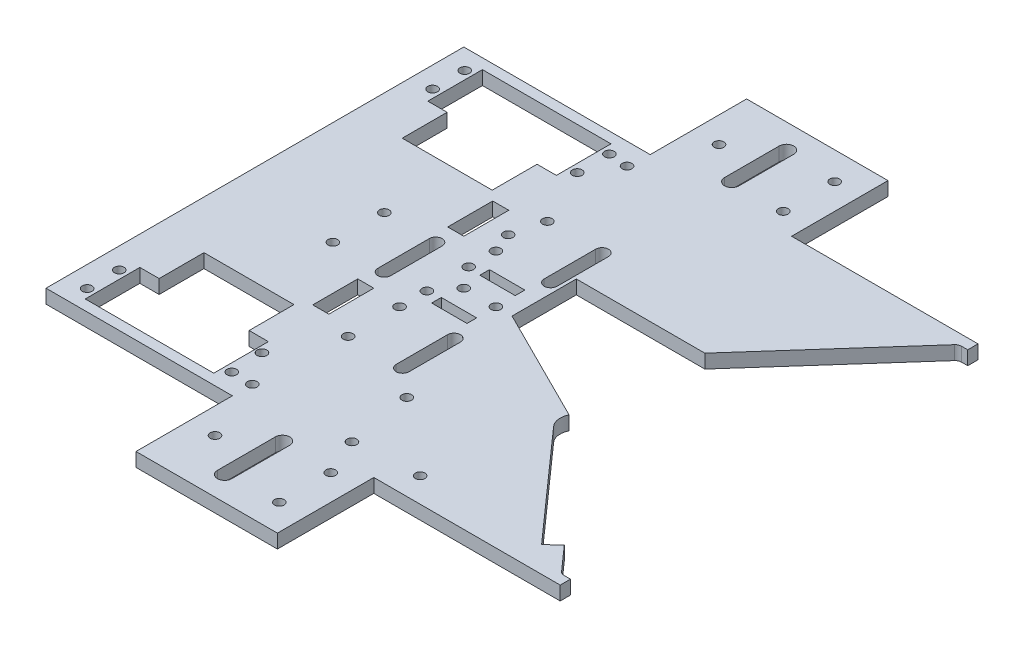
SolidWorks part; units mm, degrees
material "Acrylic (Medium-high impact)"
ref_plane "Front Plane" through (0, 0, 0) normal (0, 0, 1) x (1, 0, 0)
ref_plane "Top Plane" through (0, 0, 0) normal (0, 1, 0) x (1, 0, 0)
ref_plane "Right Plane" through (0, 0, 0) normal (1, 0, 0) x (0, 0, -1)
sketch "Sketch2" plane through (0, 0, 0) normal (0, 1, 0) x (1, 0, 0)
  line L2 (0, 0) -> (0, 65)
  line L3 (0, 65) -> (58, 65)
  line L4 (160, 0) -> (160, 65)
  line L8 (0, 0) -> (160, 0)
  line L9 (102, 65) -> (160, 65)
  line L11 (102, 65) -> (102, 95)
  line L12 (58, 65) -> (58, 95)
  line L13 (58, 95) -> (102, 95)
  dimension "D1" = 65
  dimension "D2" = 160
  dimension "D3" = 44
  dimension "D4" = 30
extrude "Boss-Extrude1" add sketch "Sketch2" along normal blind 4.3
mirror "Mirror1" about plane through (0, 4.3, 0) normal (0, 0, -1) of bodies 101
sketch "Sketch3" plane through (0, 4.3, 0) normal (0, 1, 0) x (1, 0, 0)
  line L0 (160, 61.8) -> (160, -61.8)
  line L1 (120.0126, 20) -> (157.1565, 61.8)
  line L3 (80.0126, 0) -> (80.0126, 20)
  line L4 (80.0126, 20) -> (120.0126, 20)
  line L12 (160, 65) -> (102, 65)
  line L13 (102, 65) -> (102, 95)
  line L15 (102, 95) -> (58, 95)
  line L16 (58, 65) -> (0, 65)
  line L17 (0, 65) -> (0, -65)
  line L18 (0, -65) -> (58, -65)
  line L20 (58, 95) -> (58, 65)
  line L22 (102, -65) -> (160, -65)
  line L23 (160, -65) -> (160, 65)
  line L36 (58, -65) -> (58, -95)
  line L38 (58, -95) -> (102, -95)
  line L39 (58, -95) -> (102, -95)
  line L40 (102, -95) -> (102, -65)
  line L42 (160, -61.8) -> (157.1556, -61.8)
  line L45 (160, 61.8) -> (157.1565, 61.8)
  line L48 (80.0126, 0) -> (120, -20)
  line L49 (120, -20) -> (157.1556, -61.8)
  line M24 (160, -65) -> (160, 65)
  dimension "D2" = 130
  dimension "D3" = 20
  dimension "D4" = 40
  dimension "D1" = 0
extrude "Cut-Extrude1" cut sketch "Sketch3" against normal blind 4.5 contours L48 L49 L1 L4 L3 M24 region at (132.7054, 4.3, -1.1594)
fillet "Fillet1" radius 2 2 edges at (157.1565, 2.15, -61.8) (157.1556, 2.15, 61.8)
ref_axis "Axis1" through (80, 4.3, 95) along (0, 0, -1)
sketch "Sketch4" plane through (0, 4.3, 0) normal (0, 1, 0) x (1, 0, 0)
  line L0 (80, -95) -> (80, 95)
  line L1 (102, -95) -> (58, -95) construction
  line L2 (102, 95) -> (58, 95) construction
ref_plane "Plane2" through (0, 4.3, 0) normal (0, 1, 0) x (1, 0, 0)
sketch "Sketch6" plane through (0, 4.3, 0) normal (0, 1, 0) x (1, 0, 0)
  line L3 (9, -61.8) -> (49, -61.8)
  line L6 (29, -45.8) -> (29, -44.8)
  line L7 (9, -44.8) -> (15, -44.8)
  line L11 (43, -44.8) -> (43, -30.8418)
  line L12 (15, -44.8) -> (15, -30.8418)
  line L13 (15, -30.8418) -> (43, -30.8418)
  line L15 (0, 0) -> (80.0126, 0)
  line L16 (80.0126, 0) -> (120, -20) construction
  line L18 (9, 44.8) -> (15, 44.8)
  line L20 (15, 30.8418) -> (43, 30.8418)
  line L21 (15, 44.8) -> (15, 30.8418)
  line L22 (43, 44.8) -> (43, 30.8418)
  line L25 (15, -45.8) -> (15, -30.8418) construction
  line L27 (9, 61.8) -> (49, 61.8)
  line L30 (4, -61.8) -> (3, -61.8)
  line L31 (0, -61.8) -> (160, -61.8) construction
  line L32 (3, -61.8) -> (4, -61.8)
  line L33 (3, -44.8) -> (3, -62.8) construction
  line L34 (3, -62.8) -> (55, -62.8) construction
  line L35 (55, -44.8) -> (55, -62.8) construction
  line L36 (4, -61.8) -> (54, -61.8) construction
  line L37 (0, 61.8) -> (160, 61.8) construction
  line L38 (54, 61.8) -> (55, 61.8)
  line L39 (54, 61.8) -> (55, 61.8)
  line L40 (43, 44.8) -> (49, 44.8)
  line L41 (4, -45.8) -> (4, -61.8) construction
  line L42 (4, -45.8) -> (54, -45.8) construction
  line L43 (43, -44.8) -> (49, -44.8)
  line L44 (3, -44.8) -> (55, -44.8) construction
  line L45 (29, -45.8) -> (29, -30.8418) construction
  line L46 (43, -45.8) -> (43, -30.8418) construction
  line L47 (54, -45.8) -> (54, -61.8) construction
  line L48 (9, -61.8) -> (49, -61.8)
  line L52 (9, 61.8) -> (9, 44.8)
  line L53 (55, 61.8) -> (54, 61.8)
  line L56 (49, 61.8) -> (49, 44.8)
  line L59 (3, -61.8) -> (4, -61.8)
  line L60 (9, -44.8) -> (9, -61.8)
  line L64 (49, -44.8) -> (49, -61.8)
  dimension "D4" = 1
  dimension "D5" = 14
  dimension "D6" = 14
extrude "Cut-Extrude2" cut sketch "Sketch6" against normal blind 10
sketch "Sketch8" plane through (0, 4.3, 0) normal (0, 1, 0) x (1, 0, 0)
  circle A0 centre (6.5, 58.8) radius 1.5
  circle A1 centre (6.5, 48.8) radius 1.5
  circle A2 centre (51.5, 48.8) radius 1.5
  circle A3 centre (51.5, 58.8) radius 1.5
  circle A4 centre (6.5, -48.7) radius 1.5
  circle A5 centre (6.5, -58.7) radius 1.5
  circle A6 centre (51.5, -58.7) radius 1.5
  circle A7 centre (51, -48.8) radius 1.5
  dimension "D7" = 3
extrude "Cut-Extrude3" cut sketch "Sketch8" against normal blind 10
sketch "Sketch9" plane through (0, 0, 0) normal (0, -1, 0) x (1, 0, 0)
  line L0 (75.75, 69.4) -> (75.75, 87.4)
  line L1 (75.75, -87.4) -> (75.75, -70.4)
  line L2 (80.25, -87.4) -> (80.25, -70.4)
  line L4 (80.25, 69.4) -> (80.25, 87.4)
  circle A0 centre (94, 70.4) radius 1.5
  circle A1 centre (66, 78.4) radius 1.5
  circle A2 centre (66, -78.4) radius 1.5
  circle A3 centre (94, -86.4) radius 1.5
  circle A4 centre (94, 86.4) radius 1.5
  circle A5 centre (94, -70.4) radius 1.5
  arc A6 (75.75, -87.4) -> (80.25, -87.4) centre (78, -87.4) ccw
  arc A7 (80.25, -70.4) -> (75.75, -70.4) centre (78, -70.4) ccw
  arc A10 (75.75, 69.4) -> (80.25, 69.4) centre (78, 69.4) ccw
  arc A12 (80.25, 87.4) -> (75.75, 87.4) centre (78, 87.4) ccw
  dimension "D1" = 3
extrude "Cut-Extrude4" cut sketch "Sketch9" against normal blind 10
sketch "Sketch7" plane through (0, 4.3, 0) normal (0, 1, 0) x (1, 0, 0)
  line L0 (0, 0) -> (80.0126, 0)
  line L1 (0, 65) -> (0, -65) construction
  line L2 (80.0126, 0) -> (80.0126, 20) construction
  line L3 (80, -95) -> (80, 95) construction
  line L4 (64, -9) -> (75, -9)
  line L5 (64, -6) -> (75, -6)
  line L6 (64, -9) -> (64, -6)
  line L7 (75, -9) -> (75, -6)
  line L8 (64, -7.5) -> (75, -7.5)
  line L9 (64, 7.5) -> (75, 7.5)
  line L10 (75, 9) -> (75, 6)
  line L11 (64, 9) -> (64, 6)
  line L12 (64, 6) -> (75, 6)
  line L13 (64, 9) -> (75, 9)
  circle A0 centre (60.0126, -6.5) radius 1.5
  circle A1 centre (60.0126, 6.5) radius 1.5
  dimension "D1" = 3
  dimension "D2" = 6.5
  dimension "D3" = 20
  dimension "D6" = 11
  dimension "D4" = 5
  dimension "D5" = 3
  dimension "D7" = 7.5
sketch "Sketch10" plane through (0, 4.3, 0) normal (0, 1, 0) x (1, 0, 0)
  line L0 (120, -20) -> (156.5589, -61.1287) construction
  line L1 (123.3218, -23.737) -> (149.8964, -53.6334)
  line L2 (116.263, -23.3218) -> (146.1593, -56.9552)
  line L3 (149.8964, -53.6334) -> (146.1593, -56.9552)
  line L4 (120, -20) -> (156.5589, -61.1287) construction
  line L5 (116.263, -23.3218) -> (152.8218, -64.4505) construction
  arc A0 (123.3218, -23.737) -> (116.263, -23.3218) centre (120, -20) ccw
  dimension "D1" = 5
  dimension "D2" = 45
extrude "Cut-Extrude5" cut sketch "Sketch10" against normal blind 10
sketch "Sketch11" plane through (0, 0, 0) normal (0, -1, 0) x (1, 0, 0)
  line L0 (0, 0) -> (80.0126, 0) construction
  line L1 (80, 95) -> (80, -95) construction
  line L2 (80.0126, 0) -> (0, 0)
  line L4 (75, 31.0313) -> (75, 15.0313)
  line L6 (79, 31.0313) -> (79, 15.0313)
  line L7 (79, -31.0313) -> (79, -15.0313)
  line L8 (75, -31.0313) -> (75, -15.0313)
  circle A0 centre (60, 31) radius 1.5
  circle A1 centre (60, 15) radius 1.5
  arc A2 (75, 31.0313) -> (79, 31.0313) centre (77, 31.0313) cw
  arc A3 (75, 15.0313) -> (79, 15.0313) centre (77, 15.0313) ccw
  arc A4 (75, -15.0313) -> (79, -15.0313) centre (77, -15.0313) cw
  arc A5 (75, -31.0313) -> (79, -31.0313) centre (77, -31.0313) ccw
  circle A6 centre (60, -15) radius 1.5
  circle A7 centre (60, -31) radius 1.5
  dimension "D1" = 3
  dimension "D2" = 16
  dimension "D3" = 15
  dimension "D4" = 20
  dimension "D5" = 15
  dimension "D6" = 4
extrude "Cut-Extrude6" cut sketch "Sketch11" against normal blind 10 contours L4 A3 L6 A2 | L8 A5 L7 A4 | A7 | A0 | A1 | A6 region at (77, 0, 23.0313) region at (77, 0, -23.0313) region at (60, 0, -31)
sketch "Sketch12" plane through (0, 0, 0) normal (0, -1, 0) x (-1, 0, 0)
  line L0 (0, 0) -> (-80.0126, 0) construction
  line L3 (-50.2627, -8) -> (-50.2627, 8)
  line L4 (-50.2627, 0) -> (-46.2627, 0)
  line L5 (-46.2627, -8) -> (-46.2627, 8)
  line L6 (0, 0) -> (-46.2627, 0)
  line L7 (0, 65) -> (0, -65) construction
  line L8 (-160, -61.8) -> (0, -61.8) construction
  line L9 (-80.0126, 0) -> (-50.2627, 0)
  line L10 (-80.0126, 0) -> (-115.5281, -17.7634) construction
  line L11 (-80.0126, 0) -> (-80.0126, 20) construction
  line L12 (-58, -65) -> (0, -65) construction
  line L13 (-58, 65) -> (0, 65) construction
  circle A0 centre (-32.2627, -8) radius 1.5
  circle A1 centre (-32.2627, 8) radius 1.5
  arc A2 (-46.2627, 8) -> (-50.2627, 8) centre (-48.2627, 8) ccw
  arc A3 (-50.2627, -8) -> (-46.2627, -8) centre (-48.2627, -8) ccw
  circle A5 centre (-32.2627, -8) radius 1.5 construction
  circle A6 centre (-32.2627, 8) radius 1.5 construction
  dimension "D1" = 3
  dimension "D8" = 8
  dimension "D9" = 8
  dimension "D2" = 8
  dimension "D3" = 14
  dimension "D4" = 4
  dimension "D5" = 61.8
  dimension "D6" = 65
  dimension "D7" = 65
extrude "Cut-Extrude7" cut sketch "Sketch12" against normal blind 10 contours A3 L5 L4 L3 | L4 L5 A2 L3 | A0 | A1 region at (48.2627, 0, 4.7958) region at (48.2627, 0, -4.7958) region at (32.2627, 0, 8) region at (32.2627, 0, -8)
extrude "Cut-Extrude8" cut sketch "Sketch7" against normal blind 9 contours A0 | L4 L7 L5 L6 | L12 L10 L13 L11 | A1
sketch "Sketch13" plane through (0, 4.3, 0) normal (0, 1, 0) x (1, 0, 0)
  line L0 (80.0126, 0) -> (59.0194, 0)
  line L1 (80, -95) -> (80, 95) construction
  circle A0 centre (65, 0) radius 1.5
  circle A1 centre (75, 0) radius 1.5
  dimension "D2" = 3
  dimension "D3" = 5
  dimension "D1" = 10
extrude "Cut-Extrude9" cut sketch "Sketch13" against normal blind 10 contours L0 A0 | L0 A0 | L0 A1 | L0 A1 region at (75, 4.3, 0.6366) region at (75, 4.3, -0.6366) region at (65, 4.3, 0.6366) region at (65, 4.3, -0.6366)
sketch "Sketch14" plane through (0, 4.3, 0) normal (0, 1, 0) x (1, 0, 0)
  circle A0 centre (57.5, 58.3) radius 1.5
  circle A2 centre (57.5, 21.3) radius 1.5
  circle A3 centre (85.5653, -38.3098) radius 1.5
  circle A4 centre (108.7541, -57.3434) radius 1.5
  dimension "D1" = 3
  dimension "D2" = 3
extrude "Cut-Extrude10" cut sketch "Sketch14" against normal blind 10
sketch "Sketch15" plane through (0, 4.3, 0) normal (0, 1, 0) x (1, 0, 0)
  line L1 (46, 28) -> (51, 28)
  line L2 (46, 28) -> (46, 14)
  line L3 (46, 14) -> (51, 14)
  line L4 (51, 28) -> (51, 14)
  line L6 (0, 65) -> (0, -65) construction
  line L7 (80.0126, 0) -> (53.7017, 0)
  line L8 (46, -14) -> (51, -14)
  line L9 (51, -28) -> (51, -14)
  line L10 (46, -28) -> (51, -28)
  line L11 (46, -28) -> (46, -14)
  arc A0 (50.2627, 8) -> (46.2627, 8) centre (48.2627, 8) ccw construction
  arc A1 (46.2627, -8) -> (50.2627, -8) centre (48.2627, -8) ccw construction
  dimension "D1" = 46
  dimension "D2" = 5
  dimension "D3" = 14
  dimension "D4" = 14
  dimension "D5" = 14
  dimension "D6" = 6
  dimension "D7" = 6
extrude "Cut-Extrude11" cut sketch "Sketch15" against normal blind 10 contours L4 L1 L2 L3 | L11 L10 L9 L8 region at (48.5, 4.3, -21) region at (48.5, 4.3, 21)
sketch "Sketch16" plane through (0, 4.3, 0) normal (0, 1, 0) x (1, 0, 0)
  circle A0 centre (89, -58.8) radius 1.5
  circle A1 centre (58, -58.8) radius 1.5
  dimension "D1" = 3
extrude "Cut-Extrude12" cut sketch "Sketch16" against normal blind 10
ref_plane "Plane3" through (44.2426, 0, 0) normal (1, 0, 0) x (0, 0, -1)
sketch "Sketch17" plane through (44.2426, 0, 0) normal (1, 0, 0) x (0, 0, -1)
  line L4 (0, 0) -> (20, 0)
  line L5 (20, 0) -> (20, 4.3)
  line L6 (20, 4.3) -> (0, 4.3)
  line L7 (0, 4.3) -> (0, 0)
  line L8 (0, 0) -> (20, 0)
  line L9 (20, 0) -> (20, 4.3)
  line L10 (20, 4.3) -> (0, 4.3)
  line L11 (0, 4.3) -> (0, 0)
  circle A0 centre (-2.83, 16.28) radius 0.5
  point P6 (0, 2.15)
  dimension "D4" = 1
  dimension "D2" = 2.83
  dimension "D3" = 14.13
  dimension "D1" = 0
